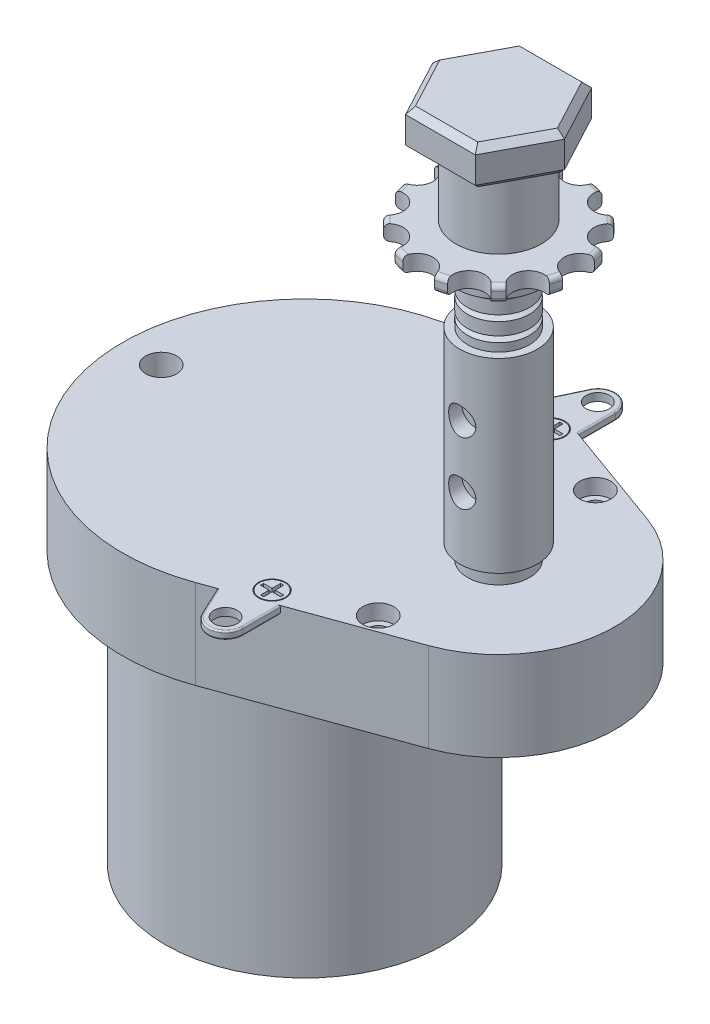
SolidWorks part; units mm, degrees
ref_plane "Front Plane" through (0, 0, 0) normal (0, 0, 1) x (1, 0, 0)
ref_plane "Top Plane" through (0, 0, 0) normal (0, 1, 0) x (1, 0, 0)
ref_plane "Right Plane" through (0, 0, 0) normal (1, 0, 0) x (0, 0, -1)
sketch "Sketch1" plane through (0, 0, 0) normal (0, 1, 0) x (1, 0, 0)
  circle A0 centre (0, 0) radius 18
  dimension "D1" = 36
extrude "Boss-Extrude1" add sketch "Sketch1" along normal blind 34
sketch "Sketch2" plane through (0, 34, 0) normal (0, 1, 0) x (1, 0, 0)
  circle A0 centre (0, 0) radius 17
  dimension "D1" = 34
extrude "Boss-Extrude2" add sketch "Sketch2" along normal blind 1
sketch "Sketch3" plane through (0, 35, 0) normal (0, 1, 0) x (1, 0, 0)
  line L0 (0, 0) -> (25, 0)
  line L1 (7.99, 22.1) -> (30.1, 14.1064)
  line L2 (7.99, -22.1) -> (30.1, -14.1064)
  circle A0 centre (0, 0) radius 23.5
  circle A1 centre (25, 0) radius 15
  circle M5 centre (0, 0) radius 17
  dimension "D1" = 47
  dimension "D2" = 30
  dimension "D3" = 25
extrude "Boss-Extrude3" add sketch "Sketch3" along normal blind 11.5 contours A1 A0 M5 | A1 L1 A0 | A1 A0 | A0 A1 L0 M5 | A1 A0 L0 M5 | A1 L0 M5 | L0 A1 M5 | A1 M5 | A1 A0 L2 region at (19.0654, 35, -6.2917) region at (13.5463, 35, 3.7961) region at (13.5463, 35, -3.7961) region at (19.0654, 35, 6.2917) region at (29.7017, 35, 0) region at (-1.5871, 35, 0) region at (-17.634, 35, 0) region at (19.2987, 35, -16.7392) region at (19.2987, 35, 16.7392)
sketch "Sketch4" plane through (0, 46.5, 0) normal (0, 1, 0) x (1, 0, 0)
  circle A1 centre (25, 0) radius 4
  dimension "D2" = 8
extrude "Boss-Extrude5" add sketch "Sketch4" along normal blind 2
sketch "Sketch5" plane through (0, 48.5, 0) normal (0, 1, 0) x (1, 0, 0)
  circle A0 centre (25, 0) radius 5
  dimension "D1" = 10
extrude "Boss-Extrude6" add sketch "Sketch5" along normal blind 24
sketch "Sketch7" plane through (0, 72.5, 0) normal (0, 1, 0) x (1, 0, 0)
  circle A0 centre (25, 0) radius 4
  dimension "D1" = 8
extrude "Boss-Extrude7" add sketch "Sketch7" along normal blind 7
sketch "Sketch8" plane through (0, 79.5, 0) normal (0, 1, 0) x (1, 0, 0)
  circle A0 centre (25, 0) radius 5.5
  dimension "D1" = 11
extrude "Boss-Extrude8" add sketch "Sketch8" along normal blind 14
sketch "Sketch9" plane through (0, 0, 0) normal (0, 0, 1) x (1, 0, 0)
  line L0 (19.5117, 79.5) -> (30.5, 79.5)
  line L1 (19.5, 79.5) -> (30.5, 79.5) construction
  line L2 (30.5, 79.5) -> (30.5, 82.5)
  line L3 (30.5, 79.5) -> (30.5, 93.5) construction
  line L4 (30.5, 82.5) -> (19.5, 82.5)
  line L5 (19.5, 93.5) -> (19.5, 79.5) construction
  line L6 (19.5, 82.5) -> (19.5117, 79.5)
  line L7 (19.5, 82.5) -> (19.5, 84.5)
  line L8 (19.5, 84.5) -> (30.5, 84.5)
  line L9 (30.5, 84.5) -> (30.5, 82.5)
  line L10 (19.5, 84.5) -> (14.5, 84.5)
  line L11 (14.5, 84.5) -> (14.5, 82.5)
  line L12 (14.5, 82.5) -> (19.5, 82.5)
  line L13 (25.0059, 79.5) -> (25.0059, 88.8611)
  dimension "D1" = 3
  dimension "D2" = 2
  dimension "D3" = 5
revolve "Revolve1" add sketch "Sketch9" angle 360 about L13 region at (17, 83.5, 0)
fillet "Fillet1" radius 0.6 1 edges at (25.0059, 84.5, -10.5059)
fillet "Fillet2" radius 0.6 1 edges at (25.0059, 82.5, -10.5059)
sketch "Sketch10" plane through (0, 84.5, 0) normal (0, 1, 0) x (1, 0, 0)
  circle A0 centre (25.0059, 0) radius 11
  circle A1 centre (25.0059, 10.505) radius 2.05
  circle M2 centre (25.0059, 0) radius 9.9059
  dimension "D1" = 4.1
  dimension "D2" = 22
  dimension "D3" = 10.505
extrude "Cut-Extrude1" cut sketch "Sketch10" against normal blind 14 contours A1 M2 | A1 A0 M2 region at (25.0059, 84.5, -10.3938) region at (25.0059, 84.5, -9.2695)
pattern_circular "CirPattern1" count 12 over 360 about axis through (25, 93.5, 0) along (0, 1, 0) of "Cut-Extrude1"
sketch "Sketch11" plane through (0, 93.5, 0) normal (0, 1, 0) x (1, 0, 0)
  line L0 (25, 0) -> (16.5, 0)
  line L1 (25, 0) -> (33.5, 0)
  line L2 (29.5, 7.5) -> (20.5, 7.5)
  line L3 (25, 0) -> (25, 13.7265) construction
  line L4 (29.5, -7.5) -> (20.5, -7.5)
  line L5 (20.5, 7.5) -> (16.5, 0)
  line L6 (20.5, -7.5) -> (16.5, 0)
  line L7 (29.5, -7.5) -> (33.5, 0)
  line L8 (29.5, 7.5) -> (33.5, 0)
  circle A0 centre (25, 0) radius 7.5
  point P10 (25, 7.5)
  circle M6 centre (25, 0) radius 5.5
  dimension "D1" = 15
  dimension "D2" = 8.5
  dimension "D3" = 8.5
  dimension "D4" = 4.5
extrude "Boss-Extrude10" add sketch "Sketch11" along normal blind 5 contours A0 L2 L5 | A0 L8 L2 | A0 L5 L0 | L3 A0 L0 M6 | L3 L1 A0 M6 | A0 L1 L8 | A0 L7 L1 | A0 L1 L0 M6 | A0 L6 L4 | A0 L0 L6 | A0 L4 L7 | L3 L1 M6 | L0 L3 M6 | L1 L0 M6 region at (25, 93.5, 2.3343) region at (27.3343, 93.5, -2.3343) region at (22.6657, 93.5, -2.3343) region at (25, 93.5, 5.6677) region at (20.8293, 93.5, -4.1707) region at (29.1707, 93.5, -4.1707) region at (17.2851, 93.5, 0.9041) region at (17.2851, 93.5, -0.9041) region at (32.7149, 93.5, -0.9041) region at (32.7149, 93.5, 0.9041) region at (21.0015, 93.5, -6.6642) region at (28.9985, 93.5, -6.6642) region at (21.0015, 93.5, 6.6642) region at (28.9985, 93.5, 6.6642)
chamfer "Chamfer1" distance 0.8 angle 45 12 edges at (25, 93.5, 7.5) (18.5, 93.5, 3.75) (18.5, 93.5, -3.75) (25, 93.5, -7.5) (31.5, 93.5, -3.75) (31.5, 93.5, 3.75) (31.5, 98.5, 3.75) (31.5, 98.5, -3.75) (25, 98.5, -7.5) (18.5, 98.5, -3.75) (18.5, 98.5, 3.75) (25, 98.5, 7.5)
sketch "Sketch13" plane through (0, 0, 0) normal (0, 0, 1) x (1, 0, 0)
  line L0 (21, 79.5) -> (29, 79.5)
  line L1 (29, 79.5) -> (29, 72.5)
  line L2 (29, 72.5) -> (21, 72.5)
  line L3 (21, 72.5) -> (21, 79.5)
  line L4 (21, 79.1127) -> (21.9094, 78.7462)
  line L5 (21.9094, 78.7462) -> (21, 78.3593)
  line L6 (21, 78.3593) -> (21, 76.6593)
  line L7 (21, 76.6593) -> (21.9094, 76.2928)
  line L8 (21.9094, 76.2928) -> (21, 75.9059)
  line L9 (21, 75.9059) -> (21, 74.3059)
  line L10 (21, 74.3059) -> (21.9094, 73.9393)
  line L11 (21.9094, 73.9393) -> (21, 73.5524)
  line L12 (25, 72.5) -> (25, 79.5)
  line L13 (21, 76.6593) -> (21, 75.9059)
  line L14 (21, 74.3059) -> (21, 73.5524)
  line L15 (21, 79.1127) -> (21, 78.3593)
  dimension "D1" = 0.3873
  dimension "D3" = 1.6
  dimension "D4" = 1.7
revolve "Cut-Revolve2" cut sketch "Sketch13" angle 360 about L12 region at (21.3031, 78.7394, 0) region at (21.3031, 76.286, 0) region at (21.3031, 73.9325, 0)
sketch "Sketch14" plane through (0, 46.5, 0) normal (0, 1, 0) x (1, 0, 0)
  line L0 (23.4794, 16.5) -> (23.4794, -16.5)
  line L1 (7.99, 22.1) -> (30.1, 14.1064) construction
  line L2 (7.99, -22.1) -> (30.1, -14.1064) construction
  line L3 (0, 0) -> (40, 0) construction
  circle A0 centre (23.4794, 14) radius 2.5
  arc A1 (30.1, -14.1064) -> (30.1, 14.1064) centre (25, 0) ccw construction
  circle A2 centre (23.4794, -14) radius 2.5
  circle A3 centre (23.4794, 14) radius 2
  circle A4 centre (23.4794, -14) radius 2
  dimension "D2" = 5
  dimension "D3" = 4
  dimension "D1" = 28
extrude "Cut-Extrude3" cut sketch "Sketch14" against normal blind 2 contours L0 A3 | L0 A3 | A4 L0 | A4 L0 region at (24.3282, 46.5, -14) region at (22.6305, 46.5, -14) region at (24.3282, 46.5, 14) region at (22.6305, 46.5, 14)
sketch "Sketch15" plane through (0, 44.5, 0) normal (0, 1, 0) x (1, 0, 0)
  circle A0 centre (23.4794, -14) radius 1.25
  circle A1 centre (23.4794, 14) radius 1.25
  dimension "D1" = 2.5
  dimension "D2" = 2.5
extrude "Cut-Extrude4" cut sketch "Sketch15" against normal blind 12
sketch "Sketch16" plane through (0, 46.5, 0) normal (0, 1, 0) x (1, 0, 0)
  line L0 (13.7985, 20) -> (13.7985, -20)
  line L1 (7.99, 22.1) -> (30.1, 14.1064) construction
  line L2 (7.99, -22.1) -> (30.1, -14.1064) construction
  line L3 (0, 0) -> (50.32, 0) construction
  circle A0 centre (0, 0) radius 23.5
  circle A1 centre (13.7985, 18) radius 2
  circle A2 centre (13.7985, -18) radius 2
  circle A3 centre (13.7985, 18) radius 1.75
  circle A4 centre (13.7985, 18) radius 1.65
  circle A5 centre (13.7985, -18) radius 1.65
  circle A6 centre (13.7985, -18) radius 1.75
  dimension "D2" = 4
  dimension "D3" = 3.5
  dimension "D4" = 3.3
  dimension "D1" = 40
extrude "Cut-Extrude5" cut sketch "Sketch16" against normal blind 0.3 contours A4 A0 A3 L0 | A4 L0 A3 A0 | A4 A0 A3 L0 | A4 L0 A3 A0 | A6 L0 A5 A0 | A6 A0 A5 L0 | A6 A0 A5 L0 | A6 L0 A5 A0 region at (15.0166, 46.5, -19.2181) region at (13.4249, 46.5, -19.6451) region at (13.0442, 46.5, -19.5022) region at (14.8916, 46.5, -16.6625) region at (12.1317, 46.5, 17.607) region at (13.4249, 46.5, 19.6451) region at (14.8916, 46.5, 16.6625) region at (13.8258, 46.5, 19.7)
sketch "Sketch17" plane through (0, 46.5, 0) normal (0, 1, 0) x (1, 0, 0)
  line L0 (13.7985, 16.7) -> (13.7985, 19.3)
  line L1 (12.4985, 18) -> (15.0985, 18)
  line L2 (13.5985, 19.3) -> (13.9985, 19.3)
  line L3 (13.9985, 19.3) -> (13.9985, 18.2)
  line L4 (13.9985, 18.2) -> (15.0985, 18.2)
  line L5 (15.0985, 18.2) -> (15.0985, 17.8)
  line L6 (13.9985, 18.2) -> (13.7985, 18)
  line L7 (12.4985, 18.2) -> (12.4985, 17.8)
  line L8 (13.5985, 18.2) -> (13.7985, 18)
  line L9 (13.5985, 18.2) -> (12.4985, 18.2)
  line L10 (13.5985, 19.3) -> (13.5985, 18.2)
  line L11 (13.5985, 16.7) -> (13.9985, 16.7)
  line L12 (13.9985, 16.7) -> (13.9985, 17.8)
  line L13 (13.9985, 17.8) -> (15.0985, 17.8)
  line L14 (13.9985, 17.8) -> (13.7985, 18)
  line L15 (13.5985, 17.8) -> (13.7985, 18)
  line L16 (13.5985, 17.8) -> (12.4985, 17.8)
  line L17 (13.5985, 16.7) -> (13.5985, 17.8)
  line L18 (0, 0) -> (40, 0)
  line L19 (13.9985, -18.2) -> (15.0985, -18.2)
  line L20 (15.0985, -18.2) -> (15.0985, -17.8)
  line L21 (13.9985, -17.8) -> (15.0985, -17.8)
  line L22 (13.9985, -16.7) -> (13.9985, -17.8)
  line L23 (13.5985, -16.7) -> (13.9985, -16.7)
  line L24 (13.5985, -16.7) -> (13.5985, -17.8)
  line L25 (13.5985, -17.8) -> (12.4985, -17.8)
  line L26 (12.4985, -18.2) -> (12.4985, -17.8)
  line L27 (13.5985, -18.2) -> (12.4985, -18.2)
  line L28 (13.5985, -19.3) -> (13.9985, -19.3)
  line L29 (13.5985, -19.3) -> (13.5985, -18.2)
  line L30 (13.9985, -19.3) -> (13.9985, -18.2)
  arc A0 (30.1, -14.1064) -> (30.1, 14.1064) centre (25, 0) ccw construction
  point P6 (13.7985, 18)
  dimension "D1" = 1.3
  dimension "D2" = 1.3
  dimension "D3" = 0.2
  dimension "D4" = 0.2
extrude "Cut-Extrude6" cut sketch "Sketch17" against normal blind 0.5 contours L2 L10 L8 L0 | L6 L3 L2 L0 | L8 L9 L7 L1 | L16 L15 L1 L7 | L17 L11 L0 L15 | L12 L14 L0 L11 | L14 L13 L5 L1 | L4 L6 L1 L5 | L28 L30 L19 L20 L21 L22 L23 L24 L25 L26 L27 L29 region at (13.7013, 46.5, -17.3014) region at (13.8957, 46.5, -17.3014) region at (13.7013, 46.5, -18.6986) region at (13.0999, 46.5, -17.9028) region at (14.4971, 46.5, -18.0972) region at (13.8957, 46.5, -18.6986) region at (13.0999, 46.5, -18.0972) region at (14.4971, 46.5, -17.9028) region at (13.7985, 46.5, 18)
sketch "Sketch18" plane through (0, 46.5, 0) normal (0, 1, 0) x (1, 0, 0)
  line L0 (13.7985, 18) -> (13.7985, 24)
  line L1 (0, 0) -> (40, 0) construction
  line L2 (16.0485, 24) -> (16.0485, -24)
  line L3 (0, 0) -> (11.8533, -25.1307)
  line L4 (16.0485, -19.1865) -> (10.0692, -21.3483)
  line L5 (7.99, 22.1) -> (30.1, 14.1064) construction
  line L6 (16.0485, 19.1865) -> (10.0692, 21.3483)
  line L7 (7.99, -22.1) -> (30.1, -14.1064) construction
  line L8 (0, 0) -> (11.8533, 25.1307)
  circle A0 centre (13.7985, 24) radius 1.5
  circle A1 centre (13.7985, 24) radius 2.25
  arc A2 (30.1, -14.1064) -> (30.1, 14.1064) centre (25, 0) ccw construction
  circle A3 centre (13.7985, -24) radius 1.5
  circle A4 centre (13.7985, -24) radius 2.25
  point P16 (10.0692, -21.3483)
  point P19 (16.0485, 19.1865)
  point P25 (16.0485, -19.1865)
  line M6 (7.99, -22.1) -> (30.1, -14.1064)
  line M8 (30.1, 14.1064) -> (7.99, 22.1)
  dimension "D2" = 3
  dimension "D3" = 4.5
  dimension "D1" = 6
extrude "Boss-Extrude12" add sketch "Sketch18" against normal blind 1 contours A1 L8 L0 M8 | A1 L0 L2 M8 | A1 L8 A0 | L3 A4 L2 M6 | A4 L3 A3 region at (11.98, 46.5, -21.7148) region at (15.0951, 46.5, -20.9504) region at (12.0039, 46.5, -22.7512) region at (13.4278, 46.5, 21.3595) region at (14.3675, 46.5, 26.111)
fillet "Fillet3" radius 0.2 12 edges at (16.0485, 45.5, -21.5933) (16.0485, 46.5, -21.5933) (16.0485, 45.5, 21.5933) (16.0485, 46.5, 21.5933) (14.384, 45.5, -26.1725) (10.9612, 45.5, -23.2395) (14.384, 46.5, -26.1725) (10.9612, 46.5, -23.2395) (14.384, 45.5, 26.1725) (10.9612, 45.5, 23.2395) (14.384, 46.5, 26.1725) (10.9612, 46.5, 23.2395)
sketch "Sketch19" plane through (0, 46.5, 0) normal (0, 1, 0) x (1, 0, 0)
  line L0 (-18.5, 0) -> (-23.5, 0)
  circle A0 centre (-18.5, 0) radius 2
  arc A1 (7.99, 22.1) -> (7.99, -22.1) centre (0, 0) ccw construction
  dimension "D1" = 4
  dimension "D2" = 5
extrude "Cut-Extrude7" cut sketch "Sketch19" against normal blind 11.5 contours A0 region at (-18.5, 46.5, 1.9434)
sketch "Sketch20" plane through (0, 35, 0) normal (0, -1, 0) x (1, 0, 0)
  circle A0 centre (25, 0) radius 7.5
  circle A1 centre (0, 0) radius 18
  circle A2 centre (0, 0) radius 18.5
  dimension "D1" = 15
  dimension "D2" = 36
  dimension "D3" = 37
extrude "Boss-Extrude13" add sketch "Sketch20" along normal blind 4 contours A2 A0 region at (25.1738, 35, 0)
sketch "Sketch21" plane through (0, 31, 0) normal (0, -1, 0) x (1, 0, 0)
  circle A0 centre (25, 0) radius 5
  dimension "D1" = 10
extrude "Cut-Extrude8" cut sketch "Sketch21" against normal blind 0.8
sketch "Sketch22" plane through (0, 31.8, 0) normal (0, -1, 0) x (1, 0, 0)
  circle A0 centre (25, 0) radius 2.25
  circle A1 centre (25, 0) radius 2
  dimension "D1" = 4.5
  dimension "D2" = 4
extrude "Cut-Extrude9" cut sketch "Sketch22" against normal blind 2
sketch "Sketch23" plane through (0, 31.8, 0) normal (0, -1, 0) x (1, 0, 0)
  circle A0 centre (25, 0) radius 2
extrude "Boss-Extrude14" add sketch "Sketch23" along normal blind 0.2
sketch "Sketch24" plane through (0, 35, 0) normal (0, -1, 0) x (1, 0, 0)
  line L0 (0, 0) -> (37.2561, 0) construction
  circle A0 centre (13.944, 17.618) radius 1
  circle A1 centre (13.944, -17.618) radius 1
  dimension "D1" = 2
extrude "Cut-Extrude10" cut sketch "Sketch24" against normal blind 4
sketch "Sketch25" plane through (0, 0, 0) normal (0, 0, 1) x (1, 0, 0)
  line L0 (25, 48.5) -> (25, 72.5) construction
  line L1 (21, 48.5) -> (29, 48.5) construction
  line L2 (30, 72.5) -> (20, 72.5) construction
  circle A0 centre (25, 64.5) radius 1.75
  circle A1 centre (25, 56.5) radius 1.75
  dimension "D3" = 3.5
  dimension "D4" = 3.5
  dimension "D1" = 8
  dimension "D2" = 8
extrude "Cut-Extrude11" cut sketch "Sketch25" against normal blind 4 and the other way blind 1 from offset 4 offset against normal yes
sketch "Sketch26" plane through (0, 0, 0) normal (0, 0, 1) x (1, 0, 0)
  line L0 (25, 72.5) -> (25, 48.5) construction
  line L1 (30, 72.5) -> (20, 72.5) construction
  line L2 (21, 48.5) -> (29, 48.5) construction
  circle A0 centre (25, 64.5) radius 1.75
  circle A1 centre (25, 56.5) radius 1.75
  dimension "D3" = 3.5
  dimension "D4" = 3.5
  dimension "D1" = 8
  dimension "D2" = 8
extrude "Cut-Extrude12" cut sketch "Sketch26" along normal blind 4 from offset 3
